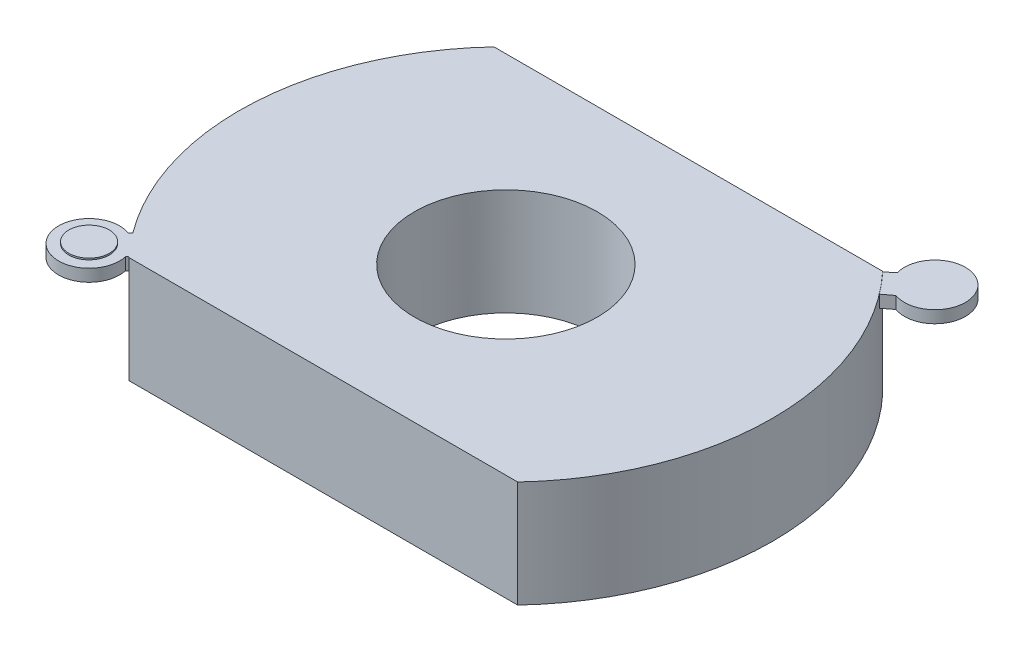
SolidWorks part; units mm, degrees
material "1345 Alloy"
ref_plane "Front Plane" through (0, 0, 0) normal (0, 0, 1) x (1, 0, 0)
ref_plane "Top Plane" through (0, 0, 0) normal (0, 1, 0) x (1, 0, 0)
ref_plane "Right Plane" through (0, 0, 0) normal (1, 0, 0) x (0, 0, -1)
sketch "Sketch1" plane through (0, 0, 0) normal (0, 1, 0) x (1, 0, 0)
  line L0 (-1712.4333, 578.2677) -> (-1658.0172, 559.892) construction
  line L1 (-1682.6566, 611.2885) -> (-1644.8226, 597.5438) construction
  line L2 (-1769.951, 660.0706) -> (-1712.4333, 741.8735) construction
  circle A0 centre (0, 0) radius 1750
  arc A3 (-1712.4333, 578.2677) -> (-1712.4333, 741.8735) centre (-1769.951, 660.0706) cw construction
  arc A4 (-1712.4333, 741.8735) -> (-1682.6566, 611.2885) centre (-1769.951, 660.0706) cw construction
extrude "Boss-Extrude1" add sketch "Sketch1" along normal blind 700
sketch "Sketch9" plane through (0, 0, 0) normal (0, -1, 0) x (1, 0, 0)
  line L1 (-2106.3119, -1198.0599) -> (2106.3119, -1198.0599)
  line L2 (-2106.3119, -1198.0599) -> (-2106.3119, 1198.0599)
  line L3 (-2106.3119, 1198.0599) -> (2106.3119, 1198.0599)
  line L4 (2106.3119, -1198.0599) -> (2106.3119, 1198.0599)
  line L5 (-2106.3119, -1198.0599) -> (2106.3119, 1198.0599) construction
  line L6 (-2106.3119, 1198.0599) -> (2106.3119, -1198.0599) construction
  line L7 (-2636.6179, -2082.9122) -> (2636.6179, -2082.9122)
  line L8 (-2636.6179, -2082.9122) -> (-2636.6179, 2082.9122)
  line L9 (-2636.6179, 2082.9122) -> (2636.6179, 2082.9122)
  line L10 (2636.6179, -2082.9122) -> (2636.6179, 2082.9122)
  line L11 (-2636.6179, -2082.9122) -> (2636.6179, 2082.9122) construction
  line L12 (-2636.6179, 2082.9122) -> (2636.6179, -2082.9122) construction
  point P0 (0, 0)
  point P6 (0, 0)
extrude "Cut-Extrude10" cut sketch "Sketch9" against normal through all both and the other way through all
sketch "Sketch3" plane through (0, 0, 0) normal (0, -1, 0) x (1, 0, 0)
  circle A0 centre (0, 0) radius 600
extrude "Cut-Extrude3" cut sketch "Sketch3" against normal through all both and the other way through all
shell "Shell1" thickness 1.5 removed face at (0, 0, 600)
sketch "Sketch12" plane through (0, 700, 0) normal (0, 1, 0) x (1, 0, 0)
  line L0 (-1280.3114, -1193.0225) -> (-1292.6188, -1204.4908)
  line L1 (-1280.3114, -1193.0225) -> (-1292.6188, -1204.4908)
  line L2 (-1420.0781, -1060.1945) -> (-1402.3021, -1046.9235)
  line L3 (-1212.6439, -1163.1539) -> (-1402.3021, -1046.9235) construction
  line L4 (-1292.6188, -1204.4908) -> (-1285.7174, -1198.0599) construction
  line L5 (1275.5989, -1198.0599) -> (-1275.5989, -1198.0599) construction
  line L6 (-1275.5989, 1198.0599) -> (1275.5989, -1198.0599) construction
  line L7 (0, 0) -> (-1750, 0) construction
  line L13 (0, 0) -> (0, 1750) construction
  line L14 (1212.6439, 1163.1539) -> (1394.7434, 1056.9725) construction
  line L15 (1331.346, 1240.5705) -> (1275.8583, 1198.0599) construction
  line L16 (1280.3114, 1193.0225) -> (1331.346, 1240.5705)
  line L17 (1280.3114, 1193.0225) -> (1331.346, 1240.5705)
  line L18 (1456.8867, 1104.0663) -> (1394.7434, 1056.9725)
  arc A0 (-1275.5989, -1198.0599) -> (-1524.5473, -859.2179) centre (0, 0) cw
  arc A1 (-1280.3114, 1193.0225) -> (-1275.5989, 1198.0599) centre (0, 0) ccw construction
  arc A2 (-1292.6188, -1204.4908) -> (-1420.0781, -1060.1945) centre (-1487.7388, -1248.402) cw
  arc A3 (-1280.3114, -1193.0225) -> (-1275.5989, -1198.0599) centre (0, 0) cw construction
  arc A4 (1275.8583, 1198.0599) -> (1394.7434, 1056.9725) centre (24.3381, 22.854) cw
  arc A6 (1331.346, 1240.5705) -> (1456.8867, 1104.0663) centre (1524.5473, 1292.2737) cw
  point P19 (-1487.7388, -1248.402)
  arc M6 (-1275.5989, 1198.0599) -> (-1275.5989, -1198.0599) centre (0, 0) ccw
extrude "Boss-Extrude2" add sketch "Sketch12" against normal blind 80 contours A2 L0 L2 M6 region at (-1487.6317, 700, 1248.1464)
extrude "Boss-Extrude3" add sketch "Sketch12<6>" against normal blind 80 separate body contours A6 L17 A4 L18 region at (1512.3148, 700, -1281.0191)
sketch "Sketch12<6>" plane through (0, 700, 0) normal (0, 1, 0) x (1, 0, 0) same geometry as "Sketch12"
sketch "Sketch13" plane through (0, 698.5, 0) normal (0, -1, 0) x (-1, 0, 0)
  line L0 (938.2248, -598.28) -> (838.2248, -598.28) construction
  line L1 (938.2248, -598.28) -> (1274.9496, -1196.5599)
  line L2 (838.2248, -598.28) -> (838.2248, -698.28) construction
  line L3 (838.2248, -698.28) -> (1038.2248, -698.28) construction
  line L4 (1038.2248, -698.28) -> (1038.2248, -498.28) construction
  line L5 (938.2248, -598.28) -> (1274.9496, -1196.5599) construction
  line L6 (1274.9496, 1196.5599) -> (938.2248, -598.28) construction
  line L7 (1274.9496, -1196.5599) -> (1274.9496, 1196.5599) construction
  line L8 (1038.2248, -498.28) -> (838.2248, -498.28) construction
  line L9 (838.2248, -498.28) -> (838.2248, -598.28) construction
  line L10 (838.2248, -498.28) -> (838.2248, -698.28)
  line L11 (838.2248, -698.28) -> (1038.2248, -698.28)
  line L12 (1038.2248, -698.28) -> (1038.2248, -498.28)
  line L13 (1038.2248, -498.28) -> (838.2248, -498.28)
  circle A1 centre (938.2248, -598.28) radius 27.5
extrude "Boss-Extrude4" add sketch "Sketch13" along normal blind 50 contours A1 L11 L12 L13 L10 region at (-916.3659, 698.5, 695.4515)
sketch "Sketch14" plane through (0, 700, 0) normal (0, 1, 0) x (1, 0, 0)
  circle A0 centre (-1487.7388, -1248.402) radius 132.8125
  point P0 (-1487.7388, -1240.2962)
extrude "Boss-Extrude5" add sketch "Sketch14" along normal blind 10
